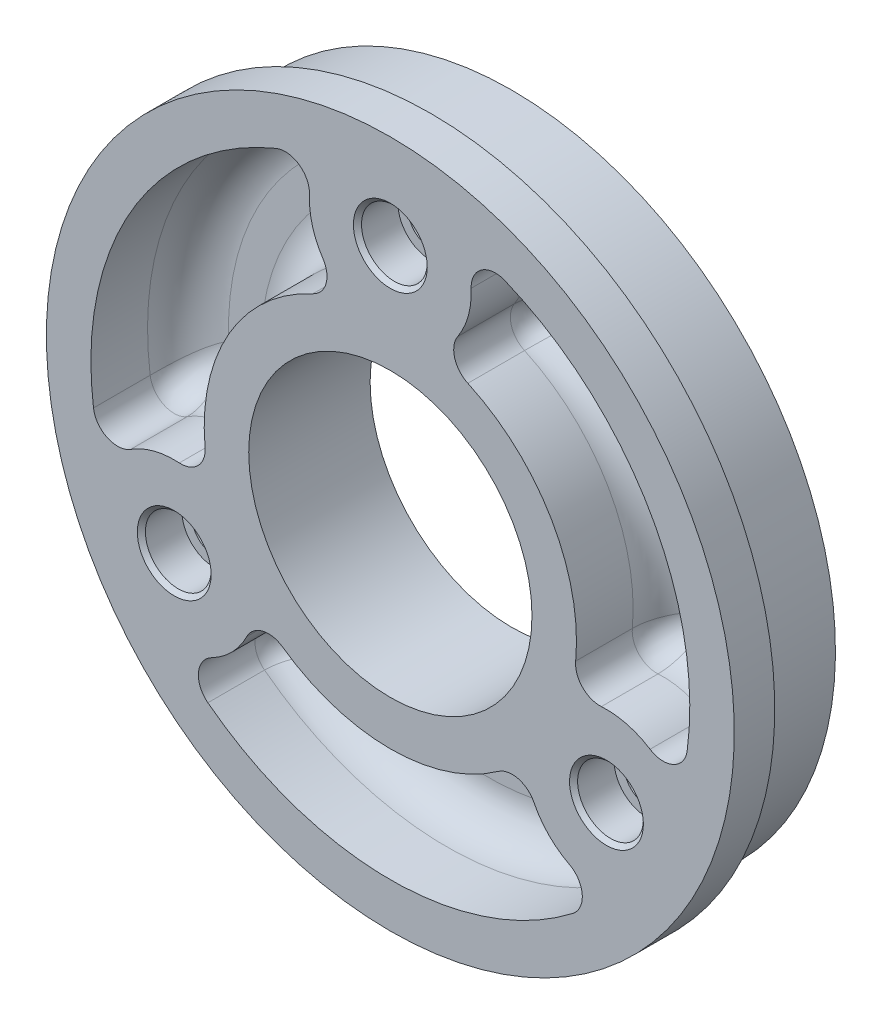
SolidWorks part; units mm, degrees
ref_plane "Front Plane" through (0, 0, 0) normal (0, 0, 1) x (1, 0, 0)
ref_plane "Top Plane" through (0, 0, 0) normal (0, 1, 0) x (1, 0, 0)
ref_plane "Right Plane" through (0, 0, 0) normal (1, 0, 0) x (0, 0, -1)
sketch "Sketch2" plane through (0, 0, 0) normal (1, 0, 0) x (0, 0, -1)
  line L0 (0, 0) -> (0, 53.975)
  line L1 (0, 53.975) -> (6.35, 53.975)
  line L2 (6.35, 53.975) -> (6.35, 50.8)
  line L3 (6.35, 50.8) -> (19.05, 50.8)
  line L4 (19.05, 50.8) -> (19.05, 0)
  line L5 (19.05, 0) -> (0, 0)
  dimension "D1" = 53.975
  dimension "D2" = 19.05
  dimension "D3" = 12.7
  dimension "D4" = 50.8
revolve "Revolve1" add sketch "Sketch2" angle 360 about L5
sketch "Sketch3" plane through (0, 0, 0) normal (0, 0, 1) x (1, 0, 0)
  point P0 (0, 39.1583)
  dimension "D1" = 39.1583
hole_wizard "CBORE for 1/4 Socket Shoulder Screw2" positions "Sketch3" profile "Sketch4" counterbore size "1/4" standard "ANSI Inch" end condition through all
sketch "Sketch4" plane through (0, 39.1583, 0) normal (1, 0, 0) x (0, -1, 0)
  line L0 (0, 0) -> (0, 19.05)
  line L1 (0, 19.05) -> (3.5712, 19.05)
  line L3 (3.5712, 19.05) -> (3.5712, 6.35)
  line L4 (3.5712, 6.35) -> (5.1587, 6.35)
  line L5 (5.1587, 6.35) -> (5.1587, 0)
  line L7 (5.1587, 0) -> (0, 0)
  line L11 (0, -6.35) -> (0, 107.95) construction
  dimension "Thru Hole Dia." = 7.1425
  dimension "Thru Hole Depth" = 19.05
  dimension "C'Bore Dia." = 10.3175
  dimension "C'Bore Depth" = 6.35
sketch "Sketch5" plane through (0, 0, 0) normal (0, 0, 1) x (1, 0, 0)
  line L0 (0, 0) -> (0, 53.975) construction
  line L1 (0, 0) -> (46.7437, 26.9875) construction
  circle A1 centre (0, 39.1583) radius 5.1587 construction
  circle A2 centre (0, 39.1583) radius 5.1587 construction
  arc A3 (17.9483, 43.4272) -> (46.5832, -6.1699) centre (0, 0) cw
  arc A4 (12.1641, 26.5567) -> (29.0808, -2.7439) centre (0, 0) cw
  arc A6 (12.1641, 26.5567) -> (10.5775, 32.1293) centre (13.7507, 30.0206) cw
  arc A7 (12.687, 39.7335) -> (10.5775, 32.1293) centre (0, 39.1583) cw
  circle A8 centre (0, 0) radius 53.975 construction
  arc A9 (17.9483, 43.4272) -> (12.687, 39.7335) centre (16.4931, 39.906) ccw
  arc A10 (29.0808, -2.7439) -> (33.1136, -6.9043) centre (32.874, -3.1018) ccw
  arc A11 (40.7537, -8.8795) -> (33.1136, -6.9043) centre (33.9121, -19.5792) ccw
  arc A12 (46.5832, -6.1699) -> (40.7537, -8.8795) centre (42.8062, -5.6696) cw
  arc A13 (28.6349, -37.2573) -> (-28.6349, -37.2573) centre (0, 0) cw
  arc A14 (28.6349, -37.2573) -> (28.0667, -30.854) centre (26.3131, -34.2364) ccw
  arc A15 (28.0667, -30.854) -> (22.5361, -25.225) centre (33.9121, -19.5792) cw
  arc A16 (16.9167, -23.8128) -> (22.5361, -25.225) centre (19.1233, -26.9188) cw
  arc A17 (16.9167, -23.8128) -> (-16.9167, -23.8128) centre (0, 0) cw
  arc A18 (-16.9167, -23.8128) -> (-22.5361, -25.225) centre (-19.1233, -26.9188) ccw
  arc A19 (-28.0667, -30.854) -> (-22.5361, -25.225) centre (-33.9121, -19.5792) ccw
  arc A20 (-28.6349, -37.2573) -> (-28.0667, -30.854) centre (-26.3131, -34.2364) cw
  arc A21 (-46.5832, -6.1699) -> (-17.9483, 43.4272) centre (0, 0) cw
  arc A22 (-46.5832, -6.1699) -> (-40.7537, -8.8795) centre (-42.8062, -5.6696) ccw
  arc A23 (-40.7537, -8.8795) -> (-33.1136, -6.9043) centre (-33.9121, -19.5792) cw
  arc A24 (-29.0808, -2.7439) -> (-33.1136, -6.9043) centre (-32.874, -3.1018) cw
  arc A25 (-29.0808, -2.7439) -> (-12.1641, 26.5567) centre (0, 0) cw
  arc A26 (-12.1641, 26.5567) -> (-10.5775, 32.1293) centre (-13.7507, 30.0206) ccw
  arc A27 (-12.687, 39.7335) -> (-10.5775, 32.1293) centre (0, 39.1583) ccw
  arc A28 (-17.9483, 43.4272) -> (-12.687, 39.7335) centre (-16.4931, 39.906) cw
  point P55 (0, 0)
  dimension "D1" = 29.21
  dimension "D2" = 46.99
  dimension "D3" = 60
  dimension "D4" = 12.7
  dimension "D5" = 3.81
  dimension "D6" = 3
extrude "Cut-Extrude1" cut sketch "Sketch5" against normal blind 15.24
sketch "Sketch7" plane through (0, 0, 0) normal (0, 0, 1) x (1, 0, 0)
  circle A13 centre (0, 0) radius 22.225
  dimension "D1" = 44.45
extrude "Cut-Extrude2" cut sketch "Sketch7" against normal through all
pattern_circular "CirPattern1" count 3 over 360 about axis through (0, 0, -19.05) along (0, 0, -1) of "CBORE for 1/4 Socket Shoulder Screw2" reverse direction yes
chamfer "Chamfer1" distance 0.635 angle 45 3 edges at (-36.4915, -15.1116, 0) (31.3327, -24.0468, 0) (5.1587, 39.1583, 0)
fillet "Fillet1" radius 6.35 24 edges at (20.0519, -23.2237, -15.24) (24.8531, -28.48, -15.24) (30.1082, -33.8997, -15.24) (0, -46.99, -15.24) (-30.1082, -33.8997, -15.24) (-24.8531, -28.48, -15.24) (-20.0519, -23.2237, -15.24) (0, -29.21, -15.24) (-30.1383, -5.7536, -15.24) (-37.0909, -7.2834, -15.24) (-44.4121, -9.1246, -15.24) (-40.6945, 23.495, -15.24) (-14.3039, 43.0243, -15.24) (-12.2378, 35.7634, -15.24) (-10.0864, 28.9773, -15.24) (-25.2966, 14.605, -15.24) (12.2378, 35.7634, -15.24) (14.3039, 43.0243, -15.24) (40.6945, 23.495, -15.24) (44.4121, -9.1246, -15.24) (37.0909, -7.2834, -15.24) (30.1383, -5.7536, -15.24) (25.2966, 14.605, -15.24) (10.0864, 28.9773, -15.24)
sketch "Sketch8" plane through (0, 0, -19.05) normal (0, 0, -1) x (-1, 0, 0)
  circle A0 centre (0, 39.1583) radius 3.5712 construction
  circle A1 centre (0, 39.1583) radius 3.5712
  circle A2 centre (0, 39.1583) radius 8.7312
  circle A3 centre (33.9121, -19.5792) radius 8.7313
  circle A4 centre (-33.9121, -19.5792) radius 8.7313
  point P10 (0, 0)
  dimension "D1" = 17.4625
  dimension "D2" = 3
extrude "Cut-Extrude3" cut sketch "Sketch8" against normal blind 7.9375
sketch "Sketch9" plane through (0, 0, -11.1125) normal (0, 0, -1) x (-1, 0, 0)
  circle A0 centre (0, 39.1583) radius 6.7469
  circle A1 centre (33.9121, -19.5792) radius 6.7469
  circle A2 centre (-33.9121, -19.5792) radius 6.7469
  point P9 (0, 0)
  dimension "D1" = 13.4937
  dimension "D2" = 3
extrude "Cut-Extrude4" cut sketch "Sketch9" against normal blind 1.27
